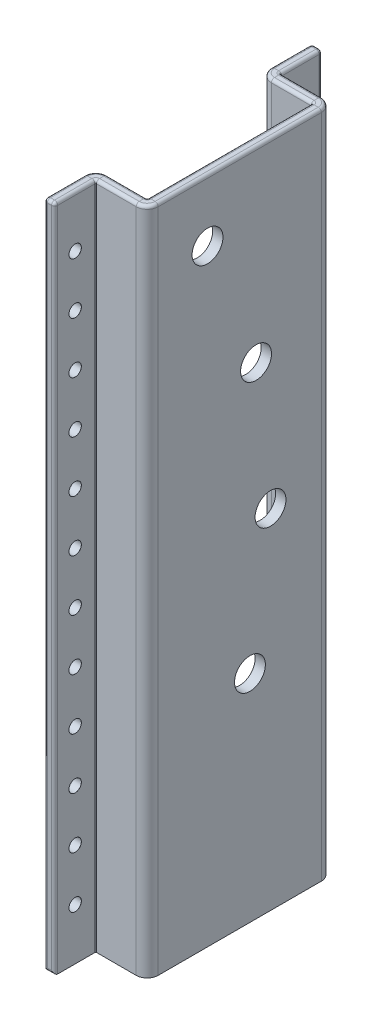
SolidWorks part; units mm, degrees
note: The reader was unsure of these and kept them because the rebuilt part matched: flange length of "Edge-Flange1", "Edge-Flange2".
material "1.0037 (S235JR)"
ref_plane "Front Plane" through (0, 0, 0) normal (0, 0, 1) x (1, 0, 0)
ref_plane "Top Plane" through (0, 0, 0) normal (0, 1, 0) x (1, 0, 0)
ref_plane "Right Plane" through (0, 0, 0) normal (1, 0, 0) x (0, 0, -1)
sketch "Sketch1" plane through (0, 0, 0) normal (1, 0, 0) x (0, 0, -1)
  line L1 (-90, 325) -> (90, 325)
  line L2 (-90, 325) -> (-90, -325)
  line L3 (-90, -325) -> (90, -325)
  line L4 (90, 325) -> (90, -325)
  point P6 (0, 325)
  point P7 (90, 0)
  dimension "D1" = 650
  dimension "D2" = 180
base flange "Base-Flange1" sketch "Sketch1" thickness 10 reverse thickness direction yes parameters "D1"=0.7366
edge flange "Edge-Flange1" sketch "Sketch10" flange profiles "Sketch10", "Sketch11" flange angle 90 flange length 60 flange position material inside bend radius 0.7366 thickness 10 relief rectangular parameters "D6"=10, "D8"=1
sketch "Sketch10" plane through (0, 0, 90) normal (0, 0, 1) x (0, 1, 0)
  line L2 (-325, 0) -> (-325, 50)
  line L3 (-325, 50) -> (325, 50)
  line L4 (325, 50) -> (325, 0)
  line L11 (325, 0) -> (-325, 0) construction
  line L12 (325, 0) -> (-325, 0)
sketch "Sketch11" plane through (0, 0, -90) normal (0, 0, -1) x (0, -1, 0)
  line L0 (325, 0) -> (-325, 0) construction
  line L1 (325, 0) -> (-325, 0)
  line L2 (-325, 0) -> (-325, 50)
  line L3 (-325, 50) -> (325, 50)
  line L4 (325, 50) -> (325, 0)
bend "EdgeBend1" bend radius 0.7366 bend angle 90 parameters "D5"=1
bend "EdgeBend2" bend radius 0.7366 bend angle 90 parameters "D5"=2
edge flange "Edge-Flange2" sketch "Sketch16" flange profiles "Sketch16", "Sketch17" flange angle 90 flange length 40 flange position material inside bend radius 0.7366 thickness 10 relief rectangular parameters "D6"=10, "D8"=1
sketch "Sketch16" plane through (-50, 0, 90) normal (-1, 0, 0) x (0, -1, 0)
  line L2 (-325, 0) -> (-325, 40)
  line L3 (-325, 40) -> (325, 40)
  line L4 (325, 40) -> (325, 0)
  line L7 (-325, 0) -> (325, 0) construction
  line L8 (-325, 0) -> (325, 0)
sketch "Sketch17" plane through (-50, 0, -90) normal (-1, 0, 0) x (0, 1, 0)
  line L0 (-325, 0) -> (325, 0) construction
  line L1 (-325, 0) -> (325, 0)
  line L2 (-325, 0) -> (-325, 40)
  line L3 (-325, 40) -> (325, 40)
  line L4 (325, 40) -> (325, 0)
bend "EdgeBend3" bend radius 0.7366 bend angle 90 parameters "D5"=3
bend "EdgeBend4" bend radius 0.7366 bend angle 90 parameters "D5"=4
sketch "Sketch18" plane through (10, 0, 0) normal (1, 0, 0) x (0, 0, -1)
  line L2 (0, 325) -> (0, -325) construction
  line L3 (79.2634, 325) -> (-79.2634, 325) construction
  line L4 (-79.2634, -325) -> (79.2634, -325) construction
  circle A4 centre (-31.3658, 265) radius 15
  circle A5 centre (15.8047, 143.2953) radius 15
  circle A6 centre (29.8684, 13.529) radius 15
  circle A7 centre (9.8669, -115.4556) radius 15
  point P28 (-470, 25)
  point P29 (-470, 25)
extrude "Cut-Extrude1" cut sketch "Sketch18" against normal blind 10 normal cut yes
hole_wizard "M10 Clearance Hole1" positions "Sketch19" profile "Sketch20" hole size "M10" standard "ANSI Metric" end condition through all
sketch "Sketch19" plane through (-40, 0, 0) normal (1, 0, 0) x (0, 0, -1)
  line L0 (-130, -325) -> (-130, 325) construction
  line L1 (-90.7366, -325) -> (-130, -325) construction
  point P0 (-110, -275)
  point P2 (-110, -225)
  point P4 (-110, -175)
  point P6 (-110, -125)
  point P8 (-110, -75)
  point P10 (-110, -25)
  point P12 (-110, 25)
  point P14 (-110, 75)
  point P16 (-110, 125)
  point P18 (-110, 175)
  point P20 (-110, 225)
  point P22 (-110, 275)
  dimension "D1" = 20
  dimension "D2" = 50
  dimension "D3" = 50
  dimension "D4" = 50
  dimension "D5" = 50
  dimension "D6" = 50
  dimension "D7" = 50
  dimension "D8" = 50
  dimension "D9" = 50
  dimension "D10" = 50
  dimension "D11" = 50
  dimension "D12" = 50
  dimension "D13" = 50
sketch "Sketch20" plane through (-40, -275, 110) normal (0, 1, 0) x (0, 0, -1)
  line L0 (0, 0) -> (0, 10)
  line L1 (0, 10) -> (6, 10)
  line L2 (6, 10) -> (6, 0.025)
  line L3 (6, 0.025) -> (6.025, 0)
  line L5 (6.025, 0) -> (0, 0)
  line L6 (-6, 0.025) -> (-6.025, 0) construction
  line L11 (0, -6.35) -> (0, 107.95) construction
  dimension "Thru Hole Dia." = 12
  dimension "Thru Hole Depth" = 10
  dimension "Near C'Sink Dia." = 12.05
  dimension "Near C'Sink Angle" = 90
mirror "Mirror1" about plane through (0, 0, 0) normal (0, 0, 1) of "M10 Clearance Hole1"
fillet "Fillet1" radius 3 26 edges at (-46.8553, 325, 83.1447) (-39.7843, 325, 90.2157) (-45, 325, 130) (-40, 325, 110.3683) (-50, 0, 130) (-50, 325, 110.3683) (-40, 0, 130) (-45, -325, 130) (-46.8553, 325, -83.1447) (-39.7843, 325, -90.2157) (-45, -325, -130) (-40, 325, -110.3683) (-50, 325, -110.3683) (-50, 0, -130) (-40, 0, -130) (-45, 325, -130) (0, 325, 0) (10, 325, 0) (6.8553, 325, 86.8553) (-0.2157, 325, 79.7843) (-20, 325, 80) (-20, 325, 90) (6.8553, 325, -86.8553) (-0.2157, 325, -79.7843) (-20, 325, -80) (-20, 325, -90)
sketch "Bend-Lines1" [suppressed] plane through (0, 0, 0) normal (0, 1, 0) x (1, 0, 0)
sketch "Bounding-Box1" [suppressed] plane through (0, 0, 0) normal (0, 1, 0) x (1, 0, 0)
sheet metal parameters "Sheet-Metal1" thickness 10 parameters "D1"=0.7366
flat pattern "Flat-Pattern1" [suppressed]
sketch "Bend-Lines2" plane through (0, 0, 0) normal (0, 1, 0) x (1, 0, 0)
sketch3d "Bounding-Box2" [suppressed]
  line L0 (75, 200, 0) -> (75, -200, 0) construction
  line L1 (-75, 200, 0) -> (-75, -200, 0) construction
  line L2 (75, 200, 0) -> (-75, 200, 0) construction
  line L3 (75, -200, 0) -> (-75, -200, 0) construction
sheet metal parameters "Sheet-Metal2" thickness 10 parameters "D1"=0.7366
flat pattern "Flat-Pattern1"
sketch "Bend-Lines2" plane through (0, 0, 0) normal (-1, 0, 0) x (0, 0, 1)
  line L0 (-68.7689, 200) -> (-68.7689, -200) construction
  line L1 (68.7689, -200) -> (68.7689, 200) construction
  line L2 (-68.7689, 200) -> (-68.7689, -200) construction
  line L3 (68.7689, -200) -> (68.7689, 200) construction
sketch3d "Bounding-Box2" [suppressed]
  line L0 (-137.5378, 200, 0) -> (-137.5378, -200, 0) construction
  line L1 (137.5378, 200, 0) -> (137.5378, -200, 0) construction
  line L2 (-137.5378, 200, 0) -> (137.5378, 200, 0) construction
  line L3 (-137.5378, -200, 0) -> (137.5378, -200, 0) construction
bend of the flat pattern "Flatten-<EdgeBend1>1"
bend of the flat pattern "Flatten-<EdgeBend2>1"
sheet metal parameters "Sheet-Metal3" thickness 10 parameters "D1"=0.7366
flat pattern "Flat-Pattern1"
sketch "Bend-Lines2" plane through (0, 0, 0) normal (-1, 0, 0) x (0, 0, 1)
  line L0 (-113.7689, 325) -> (-113.7689, -325) construction
  line L1 (113.7689, -325) -> (113.7689, 325) construction
  line L2 (-113.7689, 325) -> (-113.7689, -325) construction
  line L3 (113.7689, -325) -> (113.7689, 325) construction
  line L4 (-181.3067, 325) -> (-181.3067, -325) construction
  line L5 (181.3067, -325) -> (181.3067, 325) construction
  line L6 (-181.3067, 325) -> (-181.3067, -325) construction
  line L7 (181.3067, -325) -> (181.3067, 325) construction
sketch3d "Bounding-Box2" [suppressed]
  line L0 (-225.0757, 325, 0) -> (-225.0757, -325, 0) construction
  line L1 (225.0757, 325, 0) -> (225.0757, -325, 0) construction
  line L2 (-225.0757, 325, 0) -> (225.0757, 325, 0) construction
  line L3 (-225.0757, -325, 0) -> (225.0757, -325, 0) construction
bend of the flat pattern "Flatten-<EdgeBend1>1"
bend of the flat pattern "Flatten-<EdgeBend2>1"
bend of the flat pattern "Flatten-<EdgeBend3>1"
bend of the flat pattern "Flatten-<EdgeBend4>1"
sheet metal parameters "Sheet-Metal7" thickness 10 parameters "D1"=0.7366
flat pattern "Flat-Pattern1"
sketch "Bend-Lines2" plane through (0, 0, 0) normal (-1, 0, 0) x (0, 0, 1)
  line L0 (-83.7689, 325) -> (-83.7689, -325) construction
  line L1 (83.7689, -325) -> (83.7689, 325) construction
  line L2 (-83.7689, 325) -> (-83.7689, -325) construction
  line L3 (83.7689, -325) -> (83.7689, 325) construction
  line L4 (-131.3067, 325) -> (-131.3067, -325) construction
  line L5 (131.3067, -325) -> (131.3067, 325) construction
  line L6 (-131.3067, 325) -> (-131.3067, -325) construction
  line L7 (131.3067, -325) -> (131.3067, 325) construction
sketch3d "Bounding-Box2" [suppressed]
  line L0 (-175.0757, 325, 0) -> (-175.0757, -325, 0) construction
  line L1 (175.0757, 325, 0) -> (175.0757, -325, 0) construction
  line L2 (-175.0757, 325, 0) -> (175.0757, 325, 0) construction
  line L3 (-175.0757, -325, 0) -> (175.0757, -325, 0) construction
bend of the flat pattern "Flatten-<EdgeBend1>1"
bend of the flat pattern "Flatten-<EdgeBend2>1"
bend of the flat pattern "Flatten-<EdgeBend3>1"
bend of the flat pattern "Flatten-<EdgeBend4>1"
sheet metal parameters "Sheet-Metal8" thickness 10 parameters "D1"=0.7366
flat pattern "Flat-Pattern1"
sketch "Bend-Lines2" plane through (0, 0, 0) normal (-1, 0, 0) x (0, 0, 1)
  line L0 (-83.7689, 325) -> (-83.7689, -325) construction
  line L1 (83.7689, -325) -> (83.7689, 325) construction
  line L2 (-83.7689, 325) -> (-83.7689, -325) construction
  line L3 (83.7689, -325) -> (83.7689, 325) construction
  line L4 (-131.3067, 325) -> (-131.3067, -325) construction
  line L5 (131.3067, -325) -> (131.3067, 325) construction
  line L6 (-131.3067, 325) -> (-131.3067, -325) construction
  line L7 (131.3067, -325) -> (131.3067, 325) construction
sketch3d "Bounding-Box2" [suppressed]
  line L0 (-175.0757, 325, 0) -> (-175.0757, -325, 0) construction
  line L1 (175.0757, 325, 0) -> (175.0757, -325, 0) construction
  line L2 (-175.0757, 325, 0) -> (175.0757, 325, 0) construction
  line L3 (-175.0757, -325, 0) -> (175.0757, -325, 0) construction
bend of the flat pattern "Flatten-<EdgeBend1>1"
bend of the flat pattern "Flatten-<EdgeBend2>1"
bend of the flat pattern "Flatten-<EdgeBend3>1"
bend of the flat pattern "Flatten-<EdgeBend4>1"
sheet metal parameters "Sheet-Metal9" thickness 10 parameters "D1"=0.7366
flat pattern "Flat-Pattern1"
sketch "Bend-Lines2" plane through (0, 0, 0) normal (-1, 0, 0) x (0, 0, 1)
  line L0 (-83.7689, -325) -> (-83.7689, 322) construction
  line L1 (83.7689, -325) -> (83.7689, 322) construction
  line L2 (-83.7689, -325) -> (-83.7689, 322) construction
  line L3 (83.7689, -325) -> (83.7689, 322) construction
  line L4 (-131.3067, -325) -> (-131.3067, 322) construction
  line L5 (131.3067, -325) -> (131.3067, 322) construction
  line L6 (-131.3067, -325) -> (-131.3067, 322) construction
  line L7 (131.3067, -325) -> (131.3067, 322) construction
sketch3d "Bounding-Box2" [suppressed]
  line L0 (175.0757, 325, 0) -> (175.0757, -325, 0) construction
  line L1 (-175.0757, 325, 0) -> (-175.0757, -325, 0) construction
  line L2 (175.0757, 325, 0) -> (-175.0757, 325, 0) construction
  line L3 (175.0757, -325, 0) -> (-175.0757, -325, 0) construction
bend of the flat pattern "Flatten-<EdgeBend1>1"
bend of the flat pattern "Flatten-<EdgeBend2>1"
bend of the flat pattern "Flatten-<EdgeBend3>1"
bend of the flat pattern "Flatten-<EdgeBend4>1"
